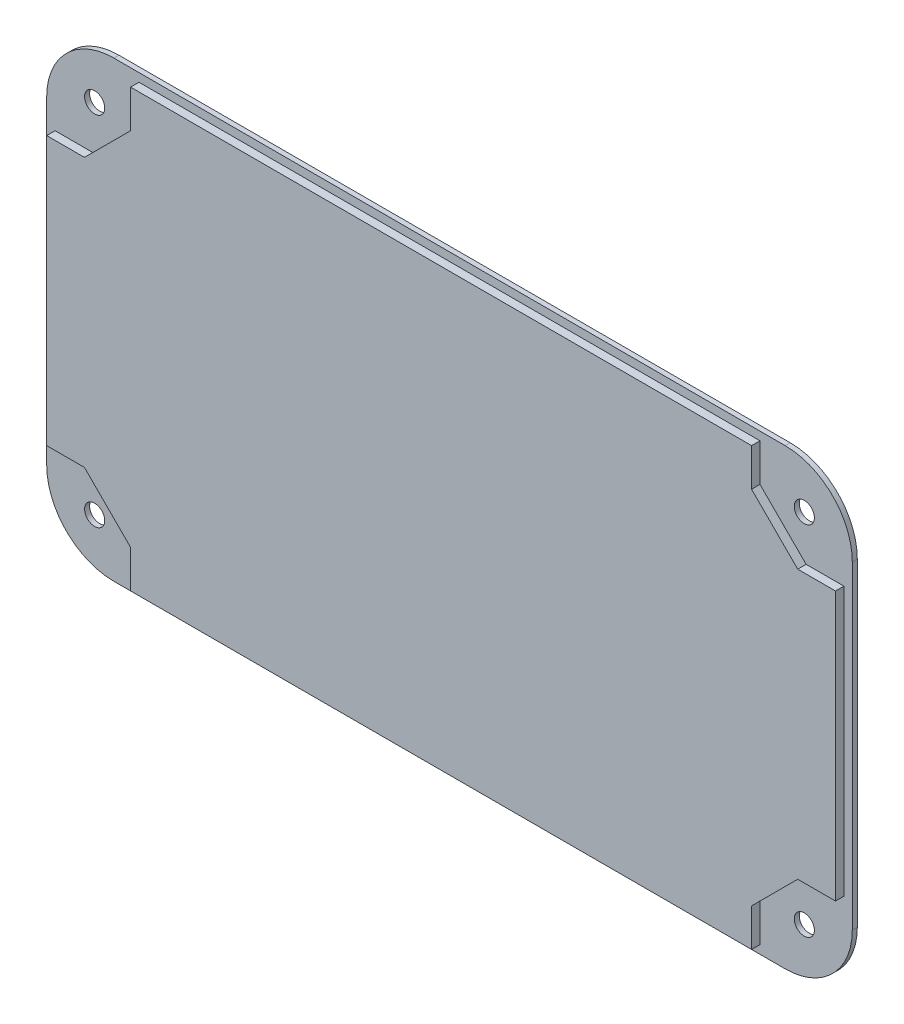
SolidWorks part; units mm, degrees
ref_plane "Front Plane" through (0, 0, 0) normal (0, 0, 1) x (1, 0, 0)
ref_plane "Top Plane" through (0, 0, 0) normal (0, 1, 0) x (1, 0, 0)
ref_plane "Right Plane" through (0, 0, 0) normal (1, 0, 0) x (0, 0, -1)
sketch "Sketch1" plane through (0, 0, 0) normal (0, 0, 1) x (1, 0, 0)
  line L1 (-100, -67.5) -> (100, -67.5)
  line L2 (-120, -47.5) -> (-120, 47.5)
  line L3 (-100, 67.5) -> (100, 67.5)
  line L4 (120, -47.5) -> (120, 47.5)
  line L5 (-120, -67.5) -> (120, 67.5) construction
  line L6 (-120, 67.5) -> (120, -67.5) construction
  arc A0 (100, -67.5) -> (120, -47.5) centre (100, -47.5) ccw
  arc A1 (100, 67.5) -> (120, 47.5) centre (100, 47.5) cw
  arc A2 (-120, 47.5) -> (-100, 67.5) centre (-100, 47.5) cw
  arc A3 (-100, -67.5) -> (-120, -47.5) centre (-100, -47.5) cw
  point P0 (0, 0)
  dimension "D3" = 20
  dimension "D1" = 135
  dimension "D2" = 240
extrude "Boss-Extrude1" add sketch "Sketch1" along normal blind 1.5
sketch "Sketch2" plane through (0, 0, 1.5) normal (0, 0, 1) x (1, 0, 0)
  line L4 (-100, -67.5) -> (100, -67.5)
  line L5 (-120, 47.5) -> (-120, -47.5)
  line L6 (100, 67.5) -> (-100, 67.5)
  line L7 (120, -47.5) -> (120, 47.5)
  line L8 (-100, -67.5) -> (100, -67.5)
  line L9 (-120, 47.5) -> (-120, -47.5)
  line L10 (100, 67.5) -> (-100, 67.5)
  line L11 (120, -47.5) -> (120, 47.5)
  line L24 (-92.5, -65) -> (92.5, -65)
  line L25 (92.5, -65) -> (92.5, -53.75)
  line L26 (92.5, -53.75) -> (106.25, -40)
  line L27 (106.25, -40) -> (117.5, -40)
  line L28 (117.5, -40) -> (117.5, 40)
  line L29 (117.5, 40) -> (106.25, 40)
  line L30 (106.25, 40) -> (92.5, 53.75)
  line L31 (92.5, 53.75) -> (92.5, 65)
  line L32 (92.5, 65) -> (-92.5, 65)
  line L33 (-92.5, 65) -> (-92.5, 53.75)
  line L34 (-92.5, 53.75) -> (-106.25, 40)
  line L35 (-106.25, 40) -> (-117.5, 40)
  line L36 (-117.5, 40) -> (-117.5, -40)
  line L37 (-117.5, -40) -> (-106.25, -40)
  line L38 (-106.25, -40) -> (-92.5, -53.75)
  line L39 (-92.5, -53.75) -> (-92.5, -65)
  line L40 (-92.5, -65) -> (92.5, -65)
  line L41 (92.5, -65) -> (92.5, -53.75)
  line L42 (92.5, -53.75) -> (106.25, -40)
  line L43 (106.25, -40) -> (117.5, -40)
  line L44 (117.5, -40) -> (117.5, 40)
  line L45 (117.5, 40) -> (106.25, 40)
  line L46 (106.25, 40) -> (92.5, 53.75)
  line L47 (92.5, 53.75) -> (92.5, 65)
  line L48 (92.5, 65) -> (-92.5, 65)
  line L49 (-92.5, 65) -> (-92.5, 53.75)
  line L50 (-92.5, 53.75) -> (-106.25, 40)
  line L51 (-106.25, 40) -> (-117.5, 40)
  line L52 (-117.5, 40) -> (-117.5, -40)
  line L53 (-117.5, -40) -> (-106.25, -40)
  line L54 (-106.25, -40) -> (-92.5, -53.75)
  line L55 (-92.5, -53.75) -> (-92.5, -65)
  circle A1 centre (105.7106, 53.2106) radius 3
  circle A2 centre (105.7106, 53.2106) radius 3
  circle A3 centre (105.7106, -53.2106) radius 3
  circle A4 centre (105.7106, -53.2106) radius 3
  circle A5 centre (-105.7106, -53.2106) radius 3
  circle A6 centre (-105.7106, -53.2106) radius 3
  circle A7 centre (-105.7106, 53.2106) radius 3
  circle A8 centre (-105.7106, 53.2106) radius 3
  arc A10 (-120, -47.5) -> (-100, -67.5) centre (-100, -47.5) ccw
  arc A11 (-100, 67.5) -> (-120, 47.5) centre (-100, 47.5) ccw
  arc A12 (120, 47.5) -> (100, 67.5) centre (100, 47.5) ccw
  arc A13 (100, -67.5) -> (120, -47.5) centre (100, -47.5) ccw
  arc A14 (-120, -47.5) -> (-100, -67.5) centre (-100, -47.5) ccw
  arc A15 (-100, 67.5) -> (-120, 47.5) centre (-100, 47.5) ccw
  arc A16 (120, 47.5) -> (100, 67.5) centre (100, 47.5) ccw
  arc A17 (100, -67.5) -> (120, -47.5) centre (100, -47.5) ccw
  dimension "D1" = 0
  dimension "D2" = 0
  dimension "D3" = 0
  dimension "D4" = 0
  dimension "D5" = 0
  dimension "D6" = 0
extrude "Cut-Extrude1" cut sketch "Sketch2" against normal through all both and the other way through all contours A2 | A4 | A6 | A8 region at (105.7106, 53.2106, 1.5) region at (105.7106, -53.2106, 1.5) region at (-105.7106, -53.2106, 1.5) region at (-105.7106, 53.2106, 1.5)
extrude "Boss-Extrude2" add sketch "Sketch2<3>" along normal blind 2.5 contours L54 L55 L40 L41 L42 L43 L44 L45 L46 L47 L48 L49 L50 L51 L52 L53 region at (0, 0, 1.5)
sketch "Sketch2<3>" plane through (0, 0, 1.5) normal (0, 0, 1) x (1, 0, 0) same geometry as "Sketch2"
